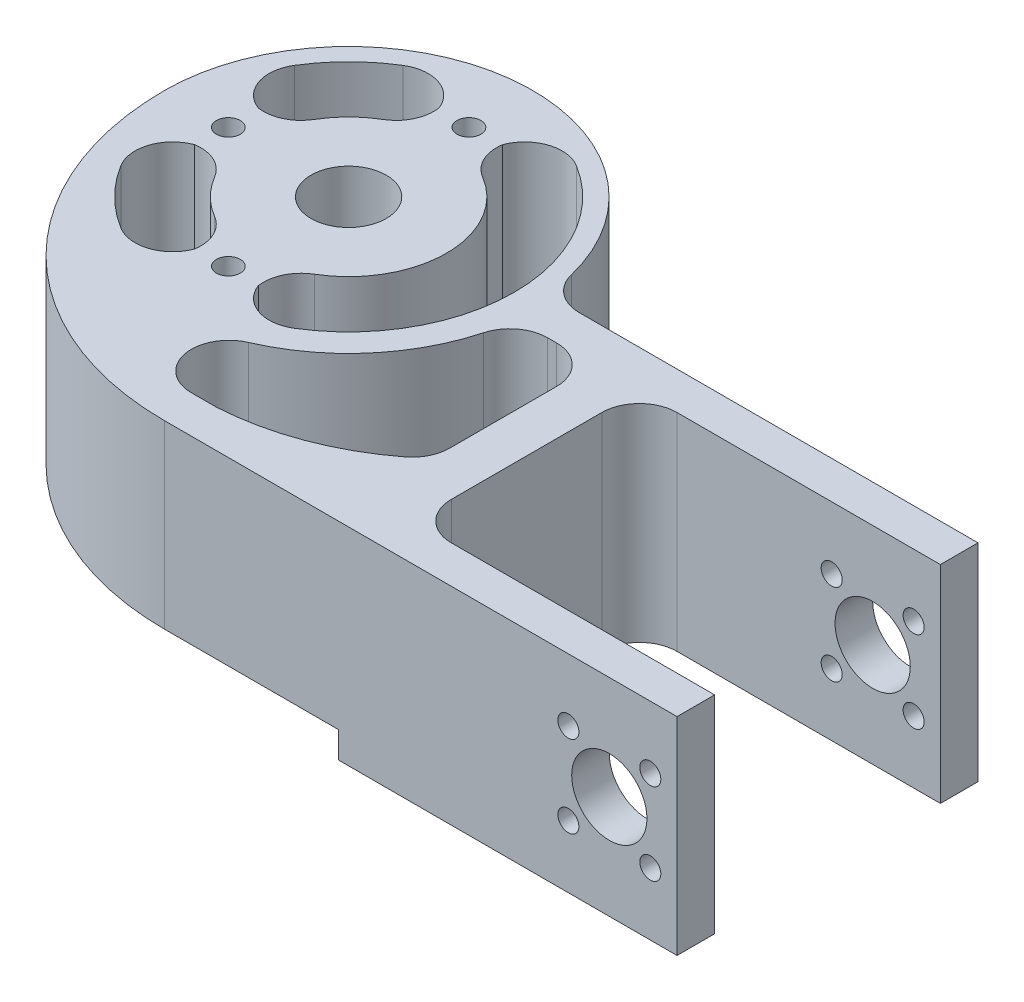
SolidWorks part; units mm, degrees
material "6061-T6 (SS)"
ref_plane "Front Plane" through (0, 0, 0) normal (0, 0, 1) x (1, 0, 0)
ref_plane "Top Plane" through (0, 0, 0) normal (0, 1, 0) x (1, 0, 0)
ref_plane "Right Plane" through (0, 0, 0) normal (1, 0, 0) x (0, 0, -1)
sketch "Sketch1" plane through (0, 0, 0) normal (0, 1, 0) x (1, 0, 0)
  circle A0 centre (0, 0) radius 31.0896
  dimension "D1" = 62.1792
extrude "Boss-Extrude1" add sketch "Sketch1" along normal blind 34.925
sketch "Sketch2" plane through (0, 34.925, 0) normal (0, 1, 0) x (1, 0, 0)
  line L0 (0, 0) -> (-31.0896, 0) construction
  line L1 (0, 0) -> (30.9857, 2.54) construction
  line L2 (46.5427, -48.26) -> (17.1704, -48.26)
  line L4 (46.5427, -48.26) -> (46.5427, 2.54)
  line L7 (30.9857, 2.54) -> (46.5427, 2.54)
  circle A0 centre (0, 0) radius 31.0896 construction
  arc A1 (17.1704, -48.26) -> (-31.0896, 0) centre (17.1704, 0) cw
  circle A2 centre (0, 0) radius 31.0896
  arc A3 (-31.0896, 0) -> (30.9857, 2.54) centre (0, 0) ccw
  dimension "D3" = 2.54
  dimension "D1" = 50.8
  dimension "D2" = 15.557
  dimension "D4" = 0
extrude "Boss-Extrude2" add sketch "Sketch2" against normal blind 30.48
sketch "Sketch3" plane through (0, 34.925, 0) normal (0, 1, 0) x (1, 0, 0)
  line L0 (46.5427, -0.3336) -> (46.5427, -48.26)
  line L1 (17.1704, -48.26) -> (46.5427, -48.26) construction
  line L2 (46.5427, -48.26) -> (103.6927, -48.26)
  line L3 (103.6927, -48.26) -> (103.6927, -41.91)
  line L4 (103.6927, -41.91) -> (52.8927, -41.91)
  line L5 (52.8927, -41.91) -> (52.8927, -3.81)
  line L6 (52.8927, -3.81) -> (103.6927, -3.81)
  line L7 (103.6927, -3.81) -> (103.6927, 2.54)
  line L8 (103.6927, 2.54) -> (46.5427, 2.54)
  line L9 (46.5427, -0.3336) -> (46.5427, 2.54)
  line L10 (46.5427, -48.26) -> (46.5427, 2.54) construction
  dimension "D1" = 57.15
  dimension "D2" = 38.1
  dimension "D3" = 6.35
  dimension "D4" = 6.35
extrude "Boss-Extrude3" add sketch "Sketch3" against normal up to surface (34.925 mm away) up to face at (0, 0, 31.0896)
sketch "Sketch4" plane through (0, 0, -2.54) normal (0, 0, -1) x (-1, 0, 0)
  line L0 (-103.6927, 17.4625) -> (-92.2627, 17.4625) construction
  line L1 (-103.6927, 0) -> (-103.6927, 34.925) construction
  line L2 (-92.2627, 17.4625) -> (-99.1775, 10.5477) construction
  line L3 (-92.2627, 17.4625) -> (-99.1775, 24.3773) construction
  line L4 (-92.2627, 17.4625) -> (-99.1775, 10.5477) construction
  line L5 (-92.2627, 17.4625) -> (-85.3479, 10.5477) construction
  line L6 (-92.2627, 17.4625) -> (-85.3479, 24.3773) construction
  line L8 (-99.1775, 24.3773) -> (-103.6927, 24.3773) construction
  line L9 (-103.6927, 0) -> (-103.6927, 34.925) construction
  line L10 (-99.1775, 10.5477) -> (-103.6927, 10.5477) construction
  circle A0 centre (-92.2627, 17.4625) radius 6.35
  circle A1 centre (-85.3479, 10.5477) radius 1.778
  circle A3 centre (-99.1775, 24.3773) radius 1.778
  circle A4 centre (-99.1775, 10.5477) radius 1.778
  circle A5 centre (-85.3479, 24.3773) radius 1.778
  dimension "D1" = 11.43
  dimension "D2" = 12.7
  dimension "D3" = 3.556
  dimension "D5" = 19.558
  dimension "D4" = 19.558
extrude "Cut-Extrude1" cut sketch "Sketch4" against normal up to surface (50.8 mm away) up to face at (53.3542, 12.7529, 48.26)
fillet "Fillet8" radius 6.35 1 edges at (30.9857, 19.685, -2.54)
fillet "Fillet9" radius 6.35 1 edges at (52.8927, 17.4625, 41.91)
fillet "Fillet10" radius 6.35 1 edges at (52.8927, 17.4625, 3.81)
sketch "Sketch6" plane through (0, 34.925, 0) normal (0, 1, 0) x (1, 0, 0)
  line L7 (103.6927, 2.54) -> (36.3688, 2.54)
  line L8 (17.1704, -48.26) -> (103.6927, -48.26)
  line L9 (103.6927, -48.26) -> (103.6927, -41.91)
  line L10 (103.6927, -41.91) -> (59.2427, -41.91)
  line L11 (52.8927, -35.56) -> (52.8927, -10.16)
  line L12 (59.2427, -3.81) -> (103.6927, -3.81)
  line L13 (103.6927, -3.81) -> (103.6927, 2.54)
  line L14 (103.6927, 2.54) -> (36.3688, 2.54)
  line L15 (17.1704, -48.26) -> (103.6927, -48.26)
  line L16 (103.6927, -48.26) -> (103.6927, -41.91)
  line L17 (103.6927, -41.91) -> (59.2427, -41.91)
  line L18 (52.8927, -35.56) -> (52.8927, -10.16)
  line L19 (59.2427, -3.81) -> (103.6927, -3.81)
  line L20 (103.6927, -3.81) -> (103.6927, 2.54)
  line L35 (59.2427, -0.635) -> (36.3688, -0.635)
  line L36 (17.1704, -45.085) -> (59.2427, -45.085)
  line L37 (49.7177, -35.56) -> (49.7177, -10.16)
  line L38 (43.6884, -0.635) -> (36.3688, -0.635)
  line L39 (17.1704, -45.085) -> (43.6884, -45.085)
  line L40 (49.7177, -35.56) -> (49.7177, -10.16)
  arc A5 (30.2004, 7.3822) -> (36.3688, 2.54) centre (36.3688, 8.89) ccw
  arc A6 (30.2004, 7.3822) -> (-31.0896, 0) centre (0, 0) ccw
  arc A7 (-31.0896, 0) -> (17.1704, -48.26) centre (17.1704, 0) ccw
  arc A8 (52.8927, -35.56) -> (59.2427, -41.91) centre (59.2427, -35.56) ccw
  arc A9 (59.2427, -3.81) -> (52.8927, -10.16) centre (59.2427, -10.16) ccw
  arc A10 (30.2004, 7.3822) -> (36.3688, 2.54) centre (36.3688, 8.89) ccw
  arc A11 (30.2004, 7.3822) -> (-31.0896, 0) centre (0, 0) ccw
  arc A12 (-31.0896, 0) -> (17.1704, -48.26) centre (17.1704, 0) ccw
  arc A13 (52.8927, -35.56) -> (59.2427, -41.91) centre (59.2427, -35.56) ccw
  arc A14 (59.2427, -3.81) -> (52.8927, -10.16) centre (59.2427, -10.16) ccw
  arc A20 (43.6884, -0.635) -> (49.9101, -8.255) centre (43.6884, -6.985) cw
  arc A21 (43.6884, -45.085) -> (49.9101, -37.465) centre (43.6884, -38.735) ccw
  arc A25 (27.1162, 6.6283) -> (36.3688, -0.635) centre (36.3688, 8.89) ccw
  arc A26 (27.1162, 6.6283) -> (-27.9146, 0) centre (0, 0) ccw
  arc A27 (-27.9146, 0) -> (17.1704, -45.085) centre (17.1704, 0) ccw
  arc A28 (49.7177, -35.56) -> (59.2427, -45.085) centre (59.2427, -35.56) ccw
  arc A29 (59.2427, -0.635) -> (49.7177, -10.16) centre (59.2427, -10.16) ccw
  arc A30 (27.1162, 6.6283) -> (36.3688, -0.635) centre (36.3688, 8.89) ccw
  arc A31 (27.1162, 6.6283) -> (-27.9146, 0) centre (0, 0) ccw
  arc A32 (-27.9146, 0) -> (17.1704, -45.085) centre (17.1704, 0) ccw
  arc A33 (49.7177, -35.56) -> (49.9101, -37.465) centre (59.2427, -35.56) ccw
  arc A34 (49.9101, -8.255) -> (49.7177, -10.16) centre (59.2427, -10.16) ccw
  line M21 (9.2497, 6.7097) -> (9.2497, -6.7097)
  arc M22 (9.2497, -6.7097) -> (6.7097, -9.2497) centre (6.7097, -6.7097) cw
  line M23 (6.7097, -9.2497) -> (-6.7097, -9.2497)
  arc M24 (-6.7097, -9.2497) -> (-9.2497, -6.7097) centre (-6.7097, -6.7097) cw
  line M25 (-9.2497, -6.7097) -> (-9.2497, 6.7097)
  arc M26 (-9.2497, 6.7097) -> (-6.7097, 9.2497) centre (-6.7097, 6.7097) cw
  line M27 (-6.7097, 9.2497) -> (6.7097, 9.2497)
  arc M28 (6.7097, 9.2497) -> (9.2497, 6.7097) centre (6.7097, 6.7097) cw
  dimension "D3" = 6.35
  dimension "D1" = 0
  dimension "D2" = 3.175
extrude "Cut-Extrude3" [suppressed] cut sketch "Sketch6" against normal blind 19.05 contours A34 A20 L38 A30 A31 A32 L39 A21 A33 L40 M28 M21 M22 M23 M24 M25 M26 M27
sketch "Sketch8" [suppressed] plane through (0, 15.875, 0) normal (0, 1, 0) x (1, 0, 0)
  line L1 (35.1127, -2.54) -> (41.4627, -2.54)
  line L2 (28.7627, -8.89) -> (28.7627, -36.83)
  line L3 (47.8127, -8.89) -> (47.8127, -36.83)
  line L6 (35.1127, -43.18) -> (41.4627, -43.18)
  line L7 (103.6927, 2.54) -> (36.3688, 2.54) construction
  line L8 (52.8927, -35.56) -> (52.8927, -10.16) construction
  line L9 (17.1704, -48.26) -> (103.6927, -48.26) construction
  arc A0 (28.7627, -36.83) -> (35.1127, -43.18) centre (35.1127, -36.83) ccw
  arc A1 (47.8127, -36.83) -> (41.4627, -43.18) centre (41.4627, -36.83) cw
  arc A2 (41.4627, -2.54) -> (47.8127, -8.89) centre (41.4627, -8.89) cw
  arc A3 (28.7627, -8.89) -> (35.1127, -2.54) centre (35.1127, -8.89) cw
  dimension "D1" = 6.35
  dimension "D2" = 5.08
  dimension "D3" = 5.08
  dimension "D4" = 19.05
  dimension "D5" = 5.08
extrude "Cut-Extrude4" [suppressed] cut sketch "Sketch8" against normal up to surface (11.43 mm away) up to face at (21.5778, 4.445, 25.8461)
sketch "Sketch9" [suppressed] plane through (0, 15.875, 0) normal (0, 1, 0) x (1, 0, 0)
  line L0 (-9.3373, 19.4097) -> (-9.3373, 18.7747)
  line L1 (-2.9873, 12.4247) -> (3.3627, 12.4247)
  line L2 (9.7127, 18.7747) -> (9.7127, 19.4097)
  line L3 (-2.9873, 25.7597) -> (3.3627, 25.7597)
  line L4 (-6.7097, 9.2497) -> (6.7097, 9.2497) construction
  line L5 (28.7627, -11.8013) -> (28.7627, -8.89) construction
  line L6 (-9.2497, -6.7097) -> (-9.2497, 6.7097) construction
  line L7 (9.2497, 6.7097) -> (9.2497, -6.7097) construction
  line L9 (-9.2497, 0) -> (9.2497, 0) construction
  line L10 (9.7127, -18.7747) -> (9.7127, -19.4097)
  line L11 (-2.9873, -12.4247) -> (3.3627, -12.4247)
  line L12 (-9.3373, -19.4097) -> (-9.3373, -18.7747)
  line L13 (-2.9873, -25.7597) -> (3.3627, -25.7597)
  arc A0 (3.3627, 12.4247) -> (9.7127, 18.7747) centre (3.3627, 18.7747) ccw
  arc A1 (-9.3373, 18.7747) -> (-2.9873, 12.4247) centre (-2.9873, 18.7747) ccw
  arc A2 (-9.3373, 19.4097) -> (-2.9873, 25.7597) centre (-2.9873, 19.4097) cw
  arc A3 (9.7127, 19.4097) -> (3.3627, 25.7597) centre (3.3627, 19.4097) ccw
  arc A4 (3.3627, -12.4247) -> (9.7127, -18.7747) centre (3.3627, -18.7747) cw
  arc A5 (-9.3373, -18.7747) -> (-2.9873, -12.4247) centre (-2.9873, -18.7747) cw
  arc A6 (-9.3373, -19.4097) -> (-2.9873, -25.7597) centre (-2.9873, -19.4097) ccw
  arc A7 (9.7127, -19.4097) -> (3.3627, -25.7597) centre (3.3627, -19.4097) cw
  dimension "D1" = 6.35
  dimension "D2" = 3.175
  dimension "D3" = 16.51
  dimension "D4" = 19.05
  dimension "D5" = 19.05
extrude "Cut-Extrude5" [suppressed] cut sketch "Sketch9" against normal up to surface (11.43 mm away) up to face at (21.5778, 4.445, 25.8461)
sketch "Sketch11" plane through (0, 4.445, 0) normal (0, -1, 0) x (-1, 0, 0)
  line L0 (-46.5427, -48.26) -> (-46.5427, 2.54)
  line L1 (-103.6927, -3.81) -> (-32.1601, -3.81)
  line L2 (-103.6927, -41.91) -> (-14.7927, -41.91)
  line L3 (-18.1864, 0) -> (-32.385, 0) construction
  line L4 (-45.2727, -3.81) -> (-45.2727, -31.1827)
  circle A0 centre (0, 0) radius 32.385
  arc A2 (-17.1704, -48.26) -> (31.0896, 0) centre (-17.1704, 0) ccw construction
  circle A3 centre (-17.1704, 0) radius 41.9774
  dimension "D1" = 64.77
  dimension "D3" = 88.9
  dimension "D2" = 14.1986
  dimension "D4" = 1.27
sketch "Sketch12" plane through (0, 0, 0) normal (0, -1, 0) x (1, 0, 0)
  line L0 (0, 0) -> (0, -20.3032) construction
  line L1 (0, 0) -> (0, 20.3032) construction
  line L2 (0, 0) -> (-20.3032, 0) construction
  line L3 (0, 0) -> (20.3032, 0) construction
  circle A0 centre (0, 20.3032) radius 2.0193
  circle A1 centre (-20.3032, 0) radius 2.0193
  circle A2 centre (0, -20.3032) radius 2.0193
  dimension "D1" = 4.0386
extrude "Cut-Extrude7" cut sketch "Sketch12" against normal up to surface (34.925 mm away) up to face at (56.2464, 34.925, 17.0919)
extrude "Cut-Extrude8" cut sketch "Sketch11" against normal through all contours L0 A3 L2 A0 L1 region at (27.27, 4.445, 26.5567)
fillet "Fillet11" radius 6.35 4 edges at (32.1601, 19.685, 3.81) (-12.1864, 19.685, 30.0047) (45.2727, 19.685, 31.1827) (45.2727, 19.685, 3.81)
sketch "Sketch14" plane through (0, 0, 0) normal (0, -1, 0) x (1, 0, 0)
  line L0 (0, 0) -> (-10.414, -10.414) construction
  line L1 (-10.414, -10.414) -> (10.414, -10.414)
  line L2 (-10.414, -10.414) -> (-10.414, 10.414)
  line L3 (-10.414, 10.414) -> (10.414, 10.414)
  line L4 (10.414, -10.414) -> (10.414, 10.414)
  line L5 (0, 0) -> (10.414, 10.414) construction
  line L6 (-10.414, 10.414) -> (0, 0) construction
  line L7 (0, 0) -> (10.414, -10.414) construction
  arc A0 (10.414, -10.414) -> (10.414, 10.414) centre (10.414, 0) ccw
  circle A1 centre (0, 0) radius 6.35
  dimension "D1" = 12.7
  dimension "D3" = 20.828
sketch "Sketch13" plane through (0, 0, 0) normal (0, -1, 0) x (1, 0, 0)
  line L0 (0, 0) -> (6.9908, 27.0513)
  line L1 (0, 0) -> (6.9908, -27.0513)
  line L2 (0, 0) -> (-6.9908, 27.0513)
  line L3 (0, 0) -> (-27.0513, 6.9908)
  line L4 (0, 0) -> (-27.0513, -6.9908)
  line L5 (0, 0) -> (-6.9908, -27.0513)
  line L6 (0, 0) -> (27.0513, 6.9908)
  line L7 (0, 0) -> (27.0513, -6.9909)
  circle A0 centre (0, 0) radius 27.94
  circle A1 centre (0, 0) radius 16.51
  circle A2 centre (0, 20.3032) radius 2.0193 construction
  circle A3 centre (0, -20.3032) radius 2.0193 construction
  circle A4 centre (-20.3032, 0) radius 2.0193 construction
  circle A5 centre (-20.3032, 0) radius 2.0193 construction
  dimension "D1" = 55.88
  dimension "D2" = 33.02
  dimension "D3" = 5.08
  dimension "D4" = 5.08
  dimension "D5" = 5.08
  dimension "D6" = 5.08
  dimension "D7" = 5.08
  dimension "D8" = 5.08
  dimension "D9" = 13.9817
extrude "Cut-Extrude9" cut sketch "Sketch13" against normal through all contours A1 L2 A0 L3 | A1 L4 A0 L5 | A1 L1 A0 L7 | A1 L6 A0 L0 | L7 A0 L6 region at (15.3134, 0, 15.3134) region at (15.3134, 0, -15.3135) region at (-15.3134, 0, 15.3134) region at (-15.3134, 0, -15.3134) region at (22.4735, 0, 0)
fillet "Fillet14" radius 6.35 12 edges at (4.1309, 17.4625, 15.9849) (6.9908, 17.4625, 27.0513) (-27.0513, 17.4625, 6.9908) (-4.1309, 17.4625, 15.9849) (-15.9849, 17.4625, 4.1309) (-6.9908, 17.4625, 27.0513) (-6.9908, 17.4625, -27.0513) (-27.0513, 17.4625, -6.9908) (-4.1309, 17.4625, -15.9849) (-15.9849, 17.4625, -4.1309) (6.9908, 17.4625, -27.0513) (4.1309, 17.4625, -15.9849)
extrude "Cut-Extrude10" cut sketch "Sketch14" against normal blind 12.7 contours L1 L4 L3 L2 | L4 A0 region at (-10.1194, 0, 0) region at (14.8338, 0, 0)
fillet "Fillet17" radius 2.54 2 edges at (13.0872, 6.35, -10.0651) (13.0872, 6.35, 10.0651)
extrude "Cut-Extrude11" cut sketch "Sketch14<3>" against normal through all contours A1 region at (0, 0, 0)
sketch "Sketch14<3>" plane through (0, 0, 0) normal (0, -1, 0) x (1, 0, 0) same geometry as "Sketch14"
